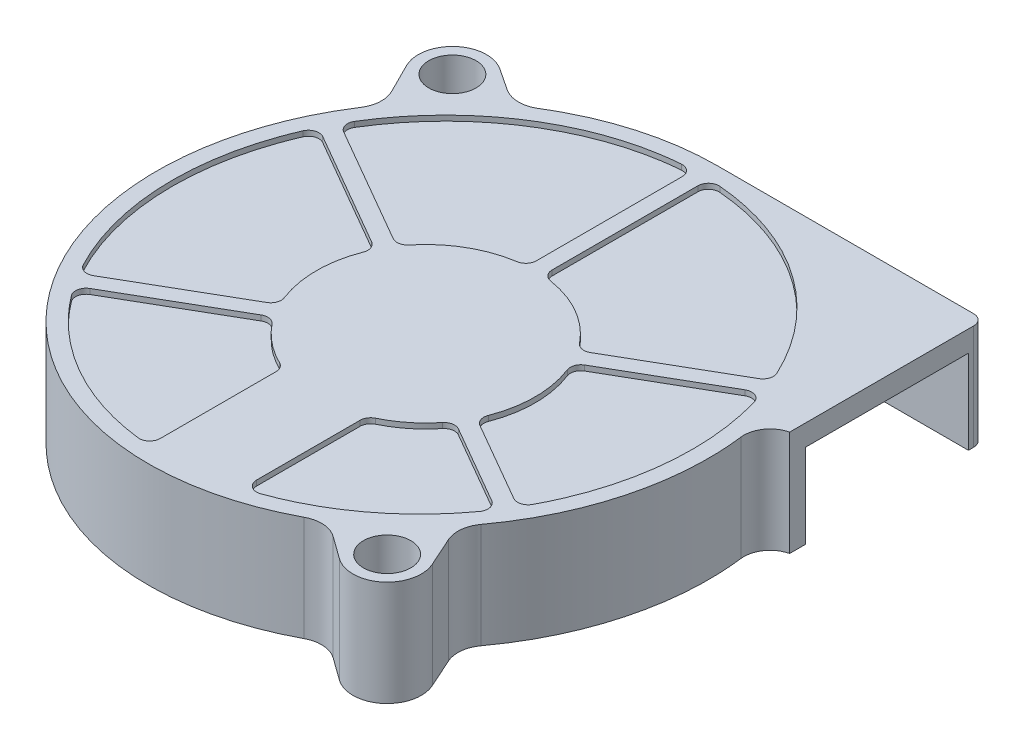
SolidWorks part; units mm, degrees
ref_plane "Front Plane" through (0, 0, 0) normal (0, 0, 1) x (1, 0, 0)
ref_plane "Top Plane" through (0, 0, 0) normal (0, 1, 0) x (1, 0, 0)
ref_plane "Right Plane" through (0, 0, 0) normal (1, 0, 0) x (0, 0, -1)
ref_plane "Plane1" through (-0.9289, 0, -30.9104) normal (0.03, 0, 0.9995) x (0, 1, 0)
sketch "Sketch18" plane through (0, 0, 0) normal (0, 1, 0) x (1, 0, 0)
  line L0 (-23.0057, 21.1739) -> (-21.5825, 18.3332)
  line L1 (14.4232, -22.6366) -> (12.2821, -21.0936)
  line L2 (-18.3115, 25.3434) -> (-16.2051, 23.9551)
  line L3 (-16.9421, 19.0744) -> (0, 0) construction
  line L4 (16.3234, -20) -> (0, 0) construction
  line L5 (-33.0815, -23.9) -> (4.114, -23.9) construction
  line L6 (-26.2, -10.7544) -> (-26.2, -0.8211) construction
  line L7 (0, 0) -> (0, -6.8242) construction
  line L8 (-4, 0) -> (-4, -27.6209) construction
  line L9 (4, 0) -> (4, -27.6209) construction
  line L10 (0, 0) -> (0, 25.466) construction
  line L11 (0.75, 0) -> (0.75, 25.466) construction
  line L12 (-0.75, 0) -> (-0.75, 25.466) construction
  line L13 (-12.8119, -19.8447) -> (10.3119, 23.6447) construction
  line L14 (-21.6522, 12.748) -> (19.1522, -8.948) construction
  line L15 (-1.25, 1.9) -> (3.3669, 1.9) construction
  line L16 (0, 0) -> (21.8429, 12.611) construction
  line L17 (0, 0) -> (-26.1434, 15.0939) construction
  line L18 (0, 0) -> (-23.531, -13.5856) construction
  line L19 (-0.0106, 27.7) -> (24.4, 27.7)
  line L20 (0, 0) -> (22.2135, -12.825) construction
  line L21 (0, 0) -> (6.1332, 0) construction
  line L22 (4, 0) -> (4, -6.8242) construction
  line L23 (-4, 0) -> (-4, -6.8242) construction
  line L24 (-1.5, 0) -> (-26.5184, 14.4444) construction
  line L25 (-1.5, 0) -> (-23.906, -12.9361) construction
  line L26 (25.4, 26.7) -> (25.4, 9.2)
  line L27 (25.4, 9.2) -> (23.0016, 9.2)
  line L28 (1.5, 0) -> (-25.7684, 15.7434) construction
  line L29 (1.5, 0) -> (-23.156, -14.2351) construction
  line L30 (9.3582, -4.5369) -> (22.5885, -12.1755) construction
  line L31 (19.2873, -18.6667) -> (18.0311, -15.874)
  line L157 (8.6082, -5.836) -> (21.8385, -13.4745) construction
  line L159 (9.3582, 4.5369) -> (22.2179, 11.9615) construction
  line L161 (8.6082, 5.836) -> (21.4679, 13.2605) construction
  line L164 (11.0633, 27.6622) -> (11.0633, 28.1486) construction
  line L165 (18.2349, 28.1486) -> (18.2349, 27.6622) construction
  line L166 (16.3586, 27.6622) -> (16.3586, 28.1486) construction
  line L167 (12.9535, 27.6622) -> (12.9535, 28.1486) construction
  line L168 (11.0633, 28.1486) -> (18.2349, 28.1486) construction
  line L169 (-26.0052, -3.975) -> (-26.3506, -3.975) construction
  line L170 (-26.3506, 3.1828) -> (-25.7716, 3.1828) construction
  line L171 (-26.1178, 1.3065) -> (-26.3506, 1.3065) construction
  line L172 (-26.0193, -2.0987) -> (-26.3506, -2.0987) construction
  line L173 (-26.3506, -3.975) -> (-26.3506, 3.1828) construction
  line L174 (19.9063, -12.0569) -> (20.36, -12.2293) construction
  line L175 (22.6116, -6.1418) -> (22.2945, -6.0236) construction
  line L176 (21.4807, -7.7289) -> (21.9583, -7.9069) construction
  line L177 (20.6345, -10.3321) -> (21.0132, -10.4642) construction
  line L178 (20.36, -12.2293) -> (22.6116, -6.1418) construction
  circle A0 centre (16.3234, -20) radius 2.25
  arc A1 (19.2873, -18.6667) -> (14.4232, -22.6366) centre (16.3234, -20) ccw construction
  circle A2 centre (-20.1, 22.6298) radius 2.25
  arc A3 (-18.3115, 25.3434) -> (-23.0057, 21.1739) centre (-20.1, 22.6298) ccw
  circle A4 centre (0, 0) radius 9.2 construction
  arc A5 (-16.2051, 23.9551) -> (-13.1979, 23.9077) centre (-14.6643, 26.293) ccw
  arc A6 (-21.5825, 18.3332) -> (-21.7386, 15.5524) centre (-24.0858, 17.079) cw
  arc A7 (-23.0057, 21.1739) -> (-18.3115, 25.3434) centre (-20.1, 22.6298) ccw construction
  arc A8 (12.2821, -21.0936) -> (9.3249, -20.8959) centre (10.6451, -23.3651) ccw
  arc A9 (25.4, 26.7) -> (24.4, 27.7) centre (24.4, 26.7) ccw
  circle A10 centre (0, 0) radius 10.4 construction
  arc A11 (18.0311, -15.874) -> (18.3294, -13.0658) centre (20.5846, -14.7253) cw
  arc A12 (14.4232, -22.6366) -> (19.2873, -18.6667) centre (16.3234, -20) ccw
  ellipse E0 centre (-1.25, 1.9) end of major axis (10.3119, 23.6447) minor radius 23.1069 construction
  ellipse E1 centre (-1.25, 1.9) end of major axis (-13.5161, -21.1691) minor radius 24.6069 (-21.7386, 15.5524) -> (9.3249, -20.8959) ccw
  ellipse E2 centre (-1.25, 1.9) end of major axis (-13.5161, -21.1691) minor radius 24.6069 (-0.0106, 27.7) -> (-13.1979, 23.9077) ccw
  ellipse E3 centre (-1.25, 1.9) end of major axis (-13.5161, -21.1691) minor radius 24.6069 (23.0016, 9.2) -> (-0.0106, 27.7) ccw construction
  ellipse E4 centre (-1.25, 1.9) end of major axis (-13.5161, -21.1691) minor radius 24.6069 (18.3294, -13.0658) -> (23.0016, 9.2) ccw
  dimension "D1" = 6.5
  dimension "D2" = 4.5
  dimension "D5" = 2.8
  dimension "D7" = 0.75
  dimension "D8" = 1
  dimension "D16" = 18.4
  dimension "D34" = 15
  dimension "D6" = 15
  dimension "D9" = 16.3234
  dimension "D10" = 20.1
  dimension "D11" = 25.4
  dimension "D12" = 27.7
  dimension "D13" = 51.6
  dimension "D14" = 20
  dimension "D15" = 51.6
  dimension "D21" = 17.5
  dimension "D22" = 28
  dimension "D23" = 0.75
  dimension "D24" = 1.9
  dimension "D25" = 1.25
  dimension "D26" = 1.5
  dimension "D27" = 1.5
  dimension "D28" = 30
  dimension "D29" = 30
  dimension "D30" = 30
  dimension "D31" = 30
  dimension "D33" = 48.388
  dimension "D17" = 4
  dimension "D18" = 4
  dimension "D19" = 1.2
  dimension "D20" = 0.75
  dimension "D32" = 0.75
extrude "Boss-Extrude3" add sketch "Sketch18" along normal blind 2 separate body
sketch "Sketch21" plane through (0, 2, 0) normal (0, -1, 0) x (1, 0, 0)
  line L2 (1.5, 0) -> (-23.156, 14.2351) construction
  line L3 (-1.5, 0) -> (-23.906, 12.9361) construction
  line L4 (8.6082, 5.836) -> (21.8385, 13.4745) construction
  line L5 (9.3582, 4.5369) -> (22.5885, 12.1755) construction
  line L6 (9.3807, 6.282) -> (16.8897, 10.6173)
  line L7 (10.1307, 4.9829) -> (17.7495, 9.3817)
  line L11 (1.5, 0) -> (-25.7684, -15.7434) construction
  line L13 (4, 0) -> (4, 27.6209) construction
  line L14 (-0.75, 0) -> (-0.75, -25.466) construction
  line L15 (4, 10.245) -> (4, 20.0877)
  line L16 (-1.5, 0) -> (-26.5184, -14.4444) construction
  line L18 (-10.1307, -4.9829) -> (-21.1393, -11.3387)
  line L19 (0.75, 0) -> (0.75, -25.466) construction
  line L20 (8.6082, -5.836) -> (21.4679, -13.2605) construction
  line L21 (9.3582, -4.5369) -> (22.2179, -11.9615) construction
  line L22 (9.3807, -6.282) -> (19.5418, -12.1485)
  line L23 (10.1307, -4.9829) -> (19.789, -10.5592)
  line L24 (-4, 10.245) -> (-4, 21.2528)
  line L25 (-9.3807, 6.282) -> (-19.697, 12.2381)
  line L26 (-10.1307, 4.9829) -> (-20.5768, 11.014)
  line L27 (-9.3807, -6.282) -> (-20.5254, -12.7164)
  line L28 (-0.75, -11.2649) -> (-0.75, -25.1306)
  line L29 (0.75, -11.2649) -> (0.75, -25.1281)
  line L30 (-4, 0) -> (-4, 27.6209) construction
  circle A0 centre (0, 0) radius 10.4 construction
  arc A1 (-4.5614, 9.3463) -> (-8.1017, 6.521) centre (0, 0) ccw
  arc A2 (8.1017, 6.521) -> (4.5614, 9.3463) centre (0, 0) ccw
  arc A3 (9.6982, -3.7558) -> (9.6982, 3.7558) centre (0, 0) ccw
  arc A4 (1.5965, -10.2767) -> (8.1017, -6.521) centre (0, 0) ccw
  arc A5 (-9.6982, 3.7558) -> (-9.6982, -3.7558) centre (0, 0) ccw
  arc A6 (-8.1017, -6.521) -> (-1.5965, -10.2767) centre (0, 0) ccw
  arc A9 (1.8322, -26.1247) -> (0.75, -25.1281) centre (1.75, -25.1281) cw
  arc A10 (-1.8301, -26.1274) -> (-0.75, -25.1306) centre (-1.75, -25.1306) ccw
  arc A11 (-0.75, -11.2649) -> (-1.5965, -10.2767) centre (-1.75, -11.2649) ccw
  arc A12 (0.75, -11.2649) -> (1.5965, -10.2767) centre (1.75, -11.2649) cw
  arc A13 (-20.8789, -14.1035) -> (-20.5254, -12.7164) centre (-20.0254, -13.5824) cw
  arc A14 (-9.3807, -6.282) -> (-8.1017, -6.521) centre (-8.8807, -7.148) cw
  arc A15 (19.5418, -12.1485) -> (19.9471, -13.4391) centre (19.0418, -13.0145) cw
  arc A16 (9.3807, -6.282) -> (8.1017, -6.521) centre (8.8807, -7.148) ccw
  arc A17 (19.789, -10.5592) -> (21.2499, -9.9702) centre (20.289, -9.6931) ccw
  arc A18 (10.1307, -4.9829) -> (9.6982, -3.7558) centre (10.6307, -4.1169) cw
  arc A19 (10.1307, 4.9829) -> (9.6982, 3.7558) centre (10.6307, 4.1169) ccw
  arc A20 (17.7495, 9.3817) -> (19.1317, 8.9866) centre (18.2495, 8.5156) cw
  arc A21 (16.8897, 10.6173) -> (17.1981, 12.0719) centre (16.3897, 11.4833) ccw
  arc A22 (9.3807, 6.282) -> (8.1017, 6.521) centre (8.8807, 7.148) cw
  arc A23 (4.5614, 9.3463) -> (4, 10.245) centre (5, 10.245) cw
  arc A24 (4, 20.0877) -> (5.3367, 21.0294) centre (5, 20.0877) cw
  arc A25 (-4, 21.2528) -> (-5.1175, 22.2459) centre (-5, 21.2528) ccw
  arc A26 (-4.5614, 9.3463) -> (-4, 10.245) centre (-5, 10.245) ccw
  arc A27 (-9.3807, 6.282) -> (-8.1017, 6.521) centre (-8.8807, 7.148) ccw
  arc A28 (-10.1307, 4.9829) -> (-9.6982, 3.7558) centre (-10.6307, 4.1169) cw
  arc A29 (-10.1307, -4.9829) -> (-9.6982, -3.7558) centre (-10.6307, -4.1169) ccw
  arc A30 (-21.1393, -11.3387) -> (-22.5567, -10.8706) centre (-21.6393, -10.4727) cw
  arc A31 (-21.9611, 10.6149) -> (-20.5768, 11.014) centre (-21.0768, 10.1479) cw
  arc A32 (-19.9944, 13.7074) -> (-19.697, 12.2381) centre (-19.197, 13.1041) ccw
  ellipse E0 centre (-1.25, -1.9) end of major axis (10.3119, -23.6447) minor radius 23.1069 construction
  ellipse E1 centre (-1.25, -1.9) end of major axis (10.3119, -23.6447) minor radius 23.1069 (-5.1175, 22.2459) -> (-19.9944, 13.7074) ccw
  ellipse E2 centre (-1.25, -1.9) end of major axis (10.3119, -23.6447) minor radius 23.1069 (17.1981, 12.0719) -> (5.3367, 21.0294) ccw
  ellipse E3 centre (-1.25, -1.9) end of major axis (10.3119, -23.6447) minor radius 23.1069 (21.2499, -9.9702) -> (19.1317, 8.9866) ccw
  ellipse E4 centre (-1.25, -1.9) end of major axis (10.3119, -23.6447) minor radius 23.1069 (1.8322, -26.1247) -> (19.9471, -13.4391) ccw
  ellipse E5 centre (-1.25, -1.9) end of major axis (10.3119, -23.6447) minor radius 23.1069 (-21.9611, 10.6149) -> (-22.5567, -10.8706) ccw
  ellipse E6 centre (-1.25, -1.9) end of major axis (10.3119, -23.6447) minor radius 23.1069 (-20.8789, -14.1035) -> (-1.8301, -26.1274) ccw
  point P84 (0.75, -10.3729)
  point P89 (-8.6082, -5.836)
  point P122 (-9.3582, 4.5369)
  point P125 (-9.3582, -4.5369)
  dimension "D1" = 1
extrude "Cut-Extrude9" cut sketch "Sketch21" along normal blind 0.5
fillet "Fillet4" radius 2.5 1 edges at (23.0016, 1, -9.2)
sketch "Sketch22" plane through (0, 0, 0) normal (0, 1, 0) x (1, 0, 0)
  line L0 (25.4, 26.2) -> (0.1345, 26.2)
  line L1 (25.4, 9.2) -> (25.4, 26.7) construction
  line L2 (24.4, 26.2) -> (-0.0106, 26.2) construction
  line L3 (25.4, 26.2) -> (25.4, 26.7)
  line L4 (25.4, 9.2) -> (25.4, 10.7302)
  line L7 (-16.2051, 23.9551) -> (-18.3115, 25.3434)
  line L8 (-23.0057, 21.1739) -> (-21.5825, 18.3332)
  line L9 (12.2821, -21.0936) -> (14.4232, -22.6366)
  line L10 (19.2873, -18.6667) -> (18.0311, -15.874)
  line L12 (25.4, 9.2) -> (25.4, 26.7)
  line L13 (24.4, 27.7) -> (-0.0106, 27.7)
  line L14 (-16.2051, 23.9551) -> (-18.3115, 25.3434)
  line L15 (-23.0057, 21.1739) -> (-21.5825, 18.3332)
  line L16 (12.2821, -21.0936) -> (14.4232, -22.6366)
  line L17 (19.2873, -18.6667) -> (18.0311, -15.874)
  line L20 (24.4, 27.7) -> (-0.0106, 27.7)
  circle A0 centre (16.3234, -20) radius 2.25 construction
  circle A1 centre (-20.1, 22.6298) radius 2.25 construction
  circle A2 centre (16.3234, -20) radius 2.25
  circle A3 centre (-20.1, 22.6298) radius 2.25
  arc A4 (21.9846, 6.4567) -> (25.4, 10.7302) centre (25.977, 6.7675) cw
  arc A8 (-16.2051, 23.9551) -> (-13.1979, 23.9077) centre (-14.6643, 26.293) ccw
  arc A9 (-18.3115, 25.3434) -> (-23.0057, 21.1739) centre (-20.1, 22.6298) ccw
  arc A10 (-21.7386, 15.5524) -> (-21.5825, 18.3332) centre (-24.0858, 17.079) ccw
  arc A11 (12.2821, -21.0936) -> (9.3249, -20.8959) centre (10.6451, -23.3651) ccw
  arc A12 (14.4232, -22.6366) -> (19.2873, -18.6667) centre (16.3234, -20) ccw
  arc A13 (18.3294, -13.0658) -> (18.0311, -15.874) centre (20.5846, -14.7253) ccw
  arc A14 (25.4, 9.2) -> (23.4964, 6.4567) centre (25.977, 6.7675) ccw
  arc A15 (25.4, 26.7) -> (24.4, 27.7) centre (24.4, 26.7) ccw
  arc A16 (-16.2051, 23.9551) -> (-13.1979, 23.9077) centre (-14.6643, 26.293) ccw
  arc A17 (-18.3115, 25.3434) -> (-23.0057, 21.1739) centre (-20.1, 22.6298) ccw
  arc A18 (-21.7386, 15.5524) -> (-21.5825, 18.3332) centre (-24.0858, 17.079) ccw
  arc A19 (12.2821, -21.0936) -> (9.3249, -20.8959) centre (10.6451, -23.3651) ccw
  arc A20 (14.4232, -22.6366) -> (19.2873, -18.6667) centre (16.3234, -20) ccw
  arc A21 (18.3294, -13.0658) -> (18.0311, -15.874) centre (20.5846, -14.7253) ccw
  arc A22 (25.4, 9.2) -> (23.4964, 6.4567) centre (25.977, 6.7675) ccw
  arc A23 (25.4, 26.7) -> (24.4, 27.7) centre (24.4, 26.7) ccw
  ellipse E0 centre (-1.25, 1.9) end of major axis (10.3119, 23.6447) minor radius 23.1069 construction
  ellipse E1 centre (-1.25, 1.9) end of major axis (10.3119, 23.6447) minor radius 23.1069 (0.1345, 26.2) -> (21.9846, 6.4567) ccw
  ellipse E2 centre (-1.25, 1.9) end of major axis (10.3119, 23.6447) minor radius 23.1069 (19.1317, -8.9866) -> (21.2499, 9.9702) ccw construction
  ellipse E3 centre (-1.25, 1.9) end of major axis (-13.5161, -21.1691) minor radius 24.6069 (-0.0106, 27.7) -> (-13.1979, 23.9077) ccw
  ellipse E4 centre (-1.25, 1.9) end of major axis (-13.5161, -21.1691) minor radius 24.6069 (-21.7386, 15.5524) -> (9.3249, -20.8959) ccw
  ellipse E5 centre (-1.25, 1.9) end of major axis (-13.5161, -21.1691) minor radius 24.6069 (18.3294, -13.0658) -> (23.4964, 6.4567) ccw
  ellipse E6 centre (-1.25, 1.9) end of major axis (-13.5161, -21.1691) minor radius 24.6069 (-0.0106, 27.7) -> (-13.1979, 23.9077) ccw
  ellipse E7 centre (-1.25, 1.9) end of major axis (-13.5161, -21.1691) minor radius 24.6069 (-21.7386, 15.5524) -> (9.3249, -20.8959) ccw
  ellipse E8 centre (-1.25, 1.9) end of major axis (-13.5161, -21.1691) minor radius 24.6069 (18.3294, -13.0658) -> (23.4964, 6.4567) ccw
  dimension "D1" = 0
  dimension "D2" = 1.5
extrude "Boss-Extrude4" add sketch "Sketch22" against normal blind 8
